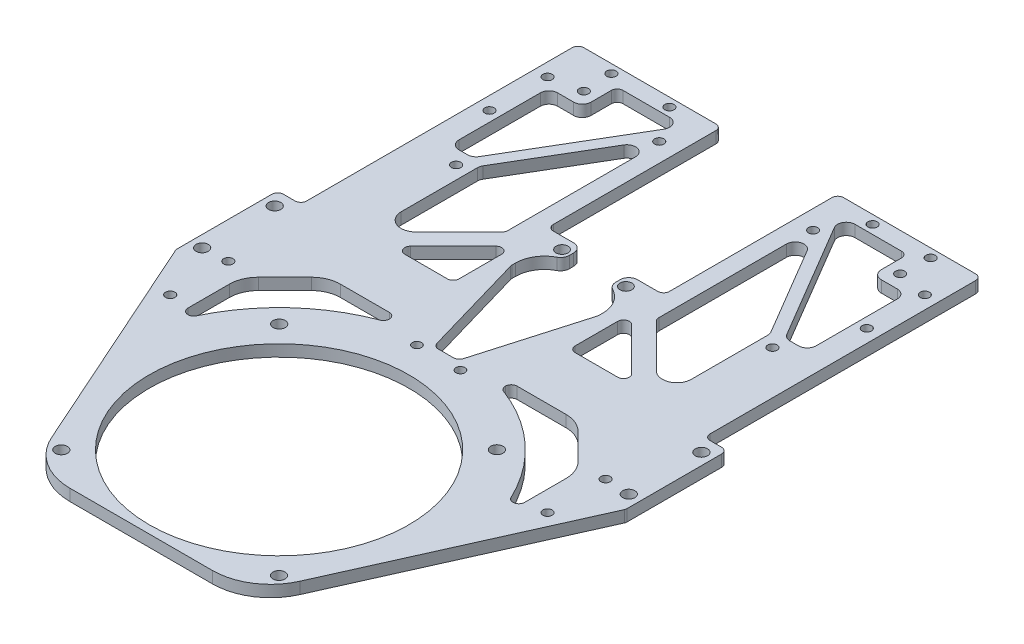
SolidWorks part; units mm, degrees
material "Thornel Mat VMA"
ref_plane "前视基准面" through (0, 0, 0) normal (0, 0, 1) x (1, 0, 0)
ref_plane "上视基准面" through (0, 0, 0) normal (0, 1, 0) x (1, 0, 0)
ref_plane "右视基准面" through (0, 0, 0) normal (1, 0, 0) x (0, 0, -1)
sketch "草图1" plane through (0, 0, 0) normal (0, 1, 0) x (1, 0, 0)
  line L1 (-77.5, 80) -> (77.5, 80)
  line L2 (-77.5, 80) -> (-77.5, -80)
  line L3 (-77.5, -80) -> (77.5, -80)
  line L4 (77.5, 80) -> (77.5, -80)
  line L5 (-77.5, 80) -> (77.5, -80) construction
  line L6 (-77.5, -80) -> (77.5, 80) construction
  line L7 (22.5, 80) -> (77.5, 80)
  line L8 (22.5, 80) -> (22.5, 140)
  line L9 (22.5, 140) -> (77.5, 140)
  line L10 (77.5, 80) -> (77.5, 140)
  line L11 (-77.5, 80) -> (-22.5, 80)
  line L12 (-77.5, 80) -> (-77.5, 140)
  line L13 (-77.5, 140) -> (-22.5, 140)
  line L14 (-22.5, 80) -> (-22.5, 140)
  point P0 (0, 0)
  dimension "D1" = 155
  dimension "D2" = 160
  dimension "D3" = 45
  dimension "D4" = 60
extrude "凸台-拉伸1" add sketch "草图1" along normal blind 4 contours L12 L1 L14 L13 | L1 L10 L9 L8 | L4 L1 L2 L3 region at (-50, 0, -110) region at (0, 0, 0) region at (50, 0, -110)
sketch "草图2" plane through (0, 4, 0) normal (0, 1, 0) x (1, 0, 0)
  line L0 (-22.5, 80) -> (22.5, 80) construction
  line L4 (-8, 87.5) -> (8, 87.5)
  line L5 (-8, 87.5) -> (-8, 72.5)
  line L6 (-8, 72.5) -> (8, 72.5)
  line L7 (8, 87.5) -> (8, 72.5)
  line L8 (-8, 87.5) -> (8, 72.5) construction
  line L9 (-8, 72.5) -> (8, 87.5) construction
  point P0 (0, 80)
  dimension "D2" = 15
  dimension "D1" = 16
extrude "切除-拉伸1" cut sketch "草图2" against normal through all
sketch "草图3" plane through (0, 4, 0) normal (0, 1, 0) x (1, 0, 0)
  line L0 (-8, 72.5) -> (8, 72.5) construction
  circle A0 centre (0, -32.5) radius 44.75
  dimension "D1" = 89.5
  dimension "D2" = 105
extrude "切除-拉伸2" cut sketch "草图3" against normal blind 5.25
sketch "草图5" plane through (0, 0, 0) normal (0, -1, 0) x (1, 0, 0)
  line L0 (37.5, 80) -> (77.5, -9.5)
  line L1 (-77.5, 80) -> (77.5, 80) construction
  line L3 (37.5, 80) -> (77.5, 80)
  line L4 (77.5, 80) -> (77.5, -9.5)
  line L5 (0, 0) -> (0, 80) construction
  line L6 (-77.5, 80) -> (-77.5, -9.5)
  line L7 (-37.5, 80) -> (-77.5, 80)
  line L8 (-37.5, 80) -> (-77.5, -9.5)
  circle A0 centre (-37.5, -5.04) radius 2.1
  circle A1 centre (-37.5, 70.04) radius 2.1
  circle A2 centre (37.5, 70.04) radius 2.1
  circle A3 centre (37.5, -5.04) radius 2.1
  dimension "D1" = 4.2
  dimension "D2" = 40
  dimension "D3" = 89.5
extrude "切除-拉伸3" cut sketch "草图5" against normal blind 10
fillet "圆角2" radius 20 2 edges at (37.5, 2, 80) (-37.5, 2, 80)
sketch "草图6" plane through (0, 4, 0) normal (0, 1, 0) x (1, 0, 0)
  line L0 (-8, 72.5) -> (8, 72.5) construction
  line L1 (-4, 25) -> (4, 25)
  line L2 (-4, 25) -> (-4, 75)
  line L3 (-4, 75) -> (4, 75)
  line L4 (4, 25) -> (4, 75)
  line L5 (-15, 72.5) -> (15, 72.5)
  line L6 (-15, 72.5) -> (-15, 62.5)
  line L7 (-15, 62.5) -> (15, 62.5)
  line L8 (15, 72.5) -> (15, 62.5)
  line L9 (-15, 72.5) -> (15, 62.5) construction
  line L10 (-15, 62.5) -> (15, 72.5) construction
  point P4 (0, 25)
  point P6 (0, 67.5)
  dimension "D1" = 25
  dimension "D2" = 8
  dimension "D3" = 50
  dimension "D4" = 10
  dimension "D5" = 30
extrude "切除-拉伸4" cut sketch "草图6" against normal through all contours L6 L5 L8 L7 | L2 L1 L4 L3
fillet "圆角1" radius 3 4 edges at (8, 2, -80) (-8, 2, -80) (-8, 2, -72.5) (8, 2, -72.5)
chamfer "倒角1" distance 11 distance2 38 1 edges at (-4, 2, -62.5) first distance on face at (-9.5, 2, -62.5)
chamfer "倒角2" distance 38 distance2 11 1 edges at (4, 2, -62.5) first distance on face at (4, 2, -43.75)
sketch "草图7" plane through (0, 4, 0) normal (0, 1, 0) x (1, 0, 0)
  line L0 (-73.5, 39.5) -> (-73.5, 14.5) construction
  line L1 (-77.5, 140) -> (-69.5, 140)
  line L2 (-77.5, 140) -> (-77.5, 44.5)
  line L3 (-77.5, 44.5) -> (-69.5, 44.5)
  line L4 (-69.5, 140) -> (-69.5, 44.5)
  line L5 (77.5, 140) -> (69.5, 140)
  line L6 (77.5, 140) -> (77.5, 44.5)
  line L7 (77.5, 44.5) -> (69.5, 44.5)
  line L8 (69.5, 140) -> (69.5, 44.5)
  line L9 (-77.5, 9.5) -> (-77.5, 140) construction
  line L10 (0, 0) -> (0, 68.6773) construction
  line L11 (73.5, 39.5) -> (73.5, 14.5) construction
  circle A0 centre (-73.5, 39.5) radius 2.1
  circle A1 centre (-73.5, 14.5) radius 2.1
  circle A2 centre (73.5, 14.5) radius 2.1
  circle A3 centre (73.5, 39.5) radius 2.1
  dimension "D4" = 4.2
  dimension "D1" = 95.5
  dimension "D2" = 8
  dimension "D3" = 4
  dimension "D5" = 25
  dimension "D6" = 5
extrude "切除-拉伸5" cut sketch "草图7" against normal through all
sketch "草图10" plane through (0, 4, 0) normal (0, 1, 0) x (1, 0, 0)
  line L0 (0, 0) -> (0, -36.4621) construction
  circle A0 centre (-11, 76) radius 2.05
  circle A1 centre (-7.5, 22.5) radius 1.55
  circle A2 centre (-54.5, 127) radius 1.6
  circle A3 centre (-54.5, 83) radius 1.6
  circle A4 centre (65, 125) radius 1.6
  circle A5 centre (65, 105) radius 1.6
  circle A6 centre (65, 15) radius 1.6
  circle A7 centre (65, -5) radius 1.6
  circle A8 centre (-65, -5) radius 1.6
  circle A9 centre (-65, 15) radius 1.6
  circle A10 centre (-65, 105) radius 1.6
  circle A11 centre (-65, 125) radius 1.6
  circle A15 centre (54.5, 83) radius 1.6
  circle A16 centre (54.5, 127) radius 1.6
  circle A19 centre (7.5, 22.5) radius 1.55
  circle A20 centre (11, 76) radius 2.05
  dimension "D1" = 4.1
  dimension "D2" = 3.1
  dimension "D3" = 3.2
extrude "切除-拉伸6" cut sketch "草图10" against normal through all
fillet "圆角3" radius 10 2 edges at (-15, 2, -72.5) (15, 2, -72.5)
fillet "圆角4" radius 2 6 edges at (-77.5, 2, -44.5) (-69.5, 2, -44.5) (77.5, 2, -44.5) (69.5, 2, -44.5) (4.1447, 2, -25) (-4.1447, 2, -25)
sketch "草图11" plane through (0, 4, 0) normal (0, 1, 0) x (1, 0, 0)
  line L0 (0, -92.5) -> (0, 140) construction
  line L1 (50, -92.5) -> (50, 140)
  line L2 (-50, -92.5) -> (-50, 140)
  line L3 (58, -92.5) -> (58, 140)
  line L4 (-58, -92.5) -> (-58, 140)
  line L5 (-58, 27.5) -> (58, 27.5)
  line L6 (20, -92.5) -> (20, 140)
  line L7 (-20, -92.5) -> (-20, 140)
  line L8 (69.5, 140) -> (-69.5, 140)
  line L9 (-58, 42.5) -> (58, 42.5)
  circle A0 centre (0, -32.5) radius 60
  dimension "D1" = 120
  dimension "D2" = 50
  dimension "D3" = 50
  dimension "D4" = 58
  dimension "D5" = 58
  dimension "D6" = 20
  dimension "D7" = 20
  dimension "D8" = 15
extrude "切除-拉伸7" cut sketch "草图11" against normal through all contours L2 L9 L7 L8 | L6 L9 L1 L8 | A0 L1 L5 L6 | A0 L3 L5 L1 | A0 L7 L5 L2 | A0 L2 L5 L4 region at (39.5193, 4, -19.495) region at (54.3337, 4, -9.9189) region at (35, 4, -91.25) region at (-39.5193, 4, -19.495) region at (-54.3337, 4, -9.9189) region at (-35, 4, -91.25)
fillet "圆角5" radius 2 3 edges at (-58, 2, 17.1377) (-20, 2, -27.5) (-20, 2, -24.0685)
fillet "圆角6" radius 2 3 edges at (20, 2, -24.0685) (20, 2, -27.5) (58, 2, 17.1377)
chamfer "倒角3" distance 35 angle 45 2 edges at (-20, 2, -42.5) (20, 2, -42.5)
sketch "草图12" plane through (0, 4, 0) normal (0, 1, 0) x (1, 0, 0)
  line L0 (-20, 77.5) -> (-50, 47.5) construction
  line L1 (50, 47.5) -> (20, 77.5) construction
  line L2 (-20, 77.5) -> (-50, 47.5)
  line L3 (50, 47.5) -> (20, 77.5)
  line L4 (-50, 47.5) -> (-20, 47.5)
  line L5 (-20, 47.5) -> (-20, 77.5)
  line L6 (20, 77.5) -> (20, 47.5)
  line L7 (20, 47.5) -> (50, 47.5)
  line L8 (-15.7574, 73.2574) -> (-45.7574, 43.2574)
  line L9 (45.7574, 43.2574) -> (15.7574, 73.2574)
  dimension "D1" = 6
extrude "切除-拉伸8" cut sketch "草图12" against normal through all contours L5 L8 L4 | L7 L9 L6 region at (-27.1716, 4, -54.6716) region at (27.1716, 4, -54.6716)
fillet "圆角7" radius 2 6 edges at (20, 2, -69.0147) (41.5147, 2, -47.5) (20, 2, -47.5) (-41.5147, 2, -47.5) (-20, 2, -69.0147) (-20, 2, -47.5)
fillet "圆角8" radius 5 2 edges at (-50, 2, -47.5) (50, 2, -47.5)
sketch "草图13" plane through (0, 4, 0) normal (0, 1, 0) x (1, 0, 0)
  line L0 (-50, 140) -> (-20, 140)
  line L1 (-20, 140) -> (-20, 77.5)
  line L2 (-50, 140) -> (-50, 134)
  line L3 (-20, 77.5) -> (-41.4645, 56.0355) construction
  line L4 (-20, 77.5) -> (-26, 71.5)
  line L5 (-50, 134) -> (-26, 134)
  line L6 (-26, 134) -> (-26, 71.5)
  line L7 (-26, 134) -> (-26, 77.5) construction
  line L8 (0, 0) -> (0, -77.25) construction
  line L9 (26, 134) -> (26, 71.5)
  line L10 (50, 134) -> (26, 134)
  line L11 (20, 140) -> (20, 77.5)
  line L12 (50, 140) -> (20, 140)
  line L13 (50, 134) -> (50, 140)
  line L14 (20, 77.5) -> (26, 71.5)
  circle A0 centre (0, -32.5) radius 44.75 construction
  dimension "D1" = 6
extrude "凸台-拉伸2" add sketch "草图13" against normal up to surface (4 mm away) up to face at (-26.7425, 0, -54.2425)
fillet "圆角12" radius 2 16 edges at (-26, 2, -134) (-26, 2, -71.5) (-50, 2, -134) (26, 2, -71.5) (26, 2, -134) (50, 2, -134) (15, 2, -62.5) (-15, 2, -62.5) (-20, 2, -80) (-20, 2, -140) (-69.5, 2, -140) (-77.5, 2, -9.5) (77.5, 2, -9.5) (20, 2, -80) (20, 2, -140) (69.5, 2, -140)
sketch "草图14" plane through (0, 0, 0) normal (0, -1, 0) x (1, 0, 0)
  line L0 (50, -59.5711) -> (50, -132) construction
  line L1 (38.5, -88) -> (61.5, -88)
  line L2 (38.5, -88) -> (38.5, -122)
  line L3 (38.5, -122) -> (61.5, -122)
  line L4 (61.5, -88) -> (61.5, -122)
  line L5 (38.5, -88) -> (61.5, -122) construction
  line L6 (38.5, -122) -> (61.5, -88) construction
  line L7 (69.5, -138) -> (69.5, -46.5) construction
  line L9 (0, 0) -> (0, 77.25) construction
  line L10 (-38.5, -122) -> (-61.5, -88) construction
  line L11 (-38.5, -88) -> (-61.5, -122) construction
  line L12 (-61.5, -88) -> (-61.5, -122)
  line L13 (-38.5, -122) -> (-61.5, -122)
  line L14 (-38.5, -88) -> (-38.5, -122)
  line L15 (-38.5, -88) -> (-61.5, -88)
  circle A0 centre (54.5, -127) radius 1.6 construction
  circle A1 centre (54.5, -83) radius 1.6 construction
  circle A2 centre (0, 32.5) radius 44.75 construction
  point P0 (50, -105)
  point P22 (-50, -105)
  dimension "D1" = 8
  dimension "D2" = 5
  dimension "D3" = 5
extrude "切除-拉伸9" cut sketch "草图14" against normal through all
sketch "草图15" plane through (0, 0, 0) normal (0, -1, 0) x (1, 0, 0)
  line L1 (53.8685, -88) -> (23.7219, -139.0175)
  line L2 (50, -86.684) -> (20.2781, -136.9825)
  line L3 (50, -88) -> (53.8685, -88)
  line L4 (61.5, -88) -> (50, -88) construction
  line L7 (50, -88) -> (50, -86.684)
  line L8 (50, -59.5711) -> (50, -88) construction
  line L9 (51.5455, -88) -> (22, -138) construction
  arc A1 (20.2781, -136.9825) -> (23.7219, -139.0175) centre (22, -138) ccw
  point P4 (38.25, -110.5)
extrude "凸台-拉伸6" add sketch "草图15" against normal blind 4
chamfer "倒角4" distance 15 angle 45 2 edges at (58, 2, -27.5) (-58, 2, -27.5)
fillet "圆角13" radius 10 4 edges at (-58, 2, -12.5) (-43, 2, -27.5) (43, 2, -27.5) (58, 2, -12.5)
mirror "镜向1" about plane through (0, 0, 0) normal (1, 0, 0) of "凸台-拉伸6"
fillet "圆角14" radius 3 14 edges at (53.8685, 2, -88) (61.5, 2, -88) (61.5, 2, -122) (50, 2, -122) (26.8867, 2, -133.6615) (50, 2, -86.684) (26, 2, -127.2994) (-50, 2, -122) (-61.5, 2, -122) (-61.5, 2, -88) (-53.8685, 2, -88) (-50, 2, -86.684) (-26, 2, -127.2994) (-26.8867, 2, -133.6615)
sketch "草图16" plane through (0, 4, 0) normal (0, 1, 0) x (1, 0, 0)
  line L0 (-20, 82) -> (-20, 138) construction
  line L1 (-67.5, 140) -> (-22, 140) construction
  line L2 (0, 0) -> (0, -183.2045) construction
  circle A0 centre (-26.5, 125) radius 4 construction
  circle A1 centre (-26.5, 125) radius 1.6
  circle A2 centre (26.5, 125) radius 4 construction
  circle A3 centre (26.5, 125) radius 1.6
  dimension "D1" = 8
  dimension "D3" = 15
  dimension "D4" = 3.2
  dimension "D2" = 6.5
extrude "切除-拉伸10" cut sketch "草图16" against normal through all
sketch "草图17" plane through (0, 4, 0) normal (0, 1, 0) x (1, 0, 0)
  circle A0 centre (-35, 137) radius 1.6
  circle A1 centre (-55, 137) radius 1.6
  circle A2 centre (55, 137) radius 1.6
  circle A3 centre (35, 137) radius 1.6
  dimension "D1" = 3.2
extrude "切除-拉伸11" cut sketch "草图17" against normal blind 10
